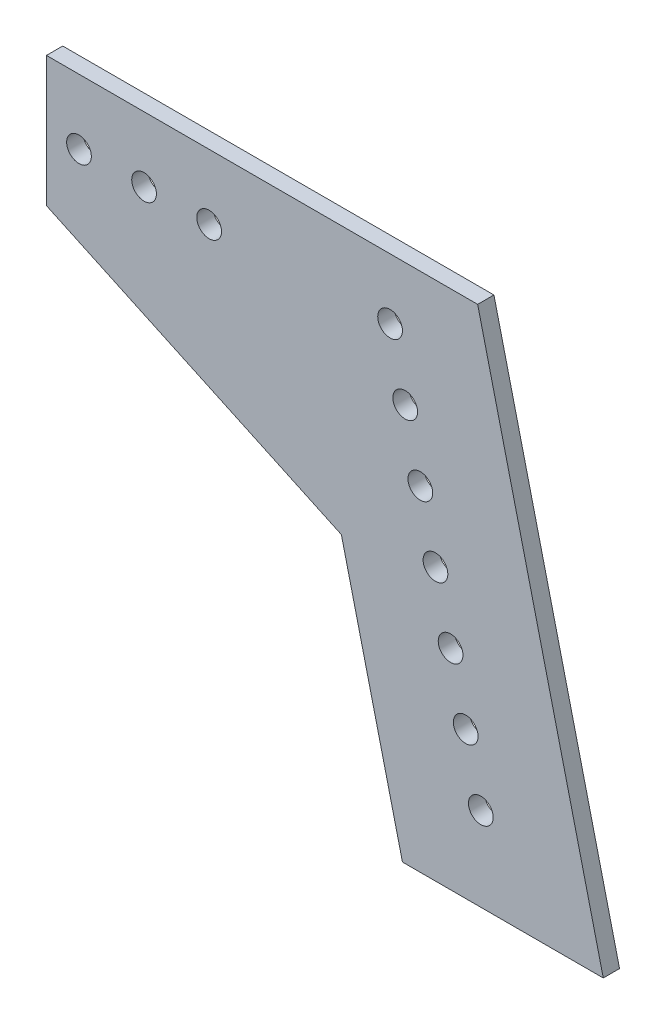
SolidWorks part; units mm, degrees
ref_plane "Front Plane" through (0, 0, 0) normal (0, 0, 1) x (1, 0, 0)
ref_plane "Top Plane" through (0, 0, 0) normal (0, 1, 0) x (1, 0, 0)
ref_plane "Right Plane" through (0, 0, 0) normal (1, 0, 0) x (0, 0, -1)
sketch "Sketch1" plane through (0, 0, 0) normal (0, 0, 1) x (1, 0, 0)
  line L1 (-190.5, -88.9) -> (190.5, -88.9)
  line L2 (-190.5, -88.9) -> (-190.5, 88.9)
  line L3 (-190.5, 88.9) -> (190.5, 88.9)
  line L4 (190.5, -88.9) -> (190.5, 88.9)
  dimension "D1" = 381
  dimension "D2" = 177.8
extrude "Boss-Extrude1" add sketch "Sketch1" along normal blind 3.175
sketch "Sketch3" plane through (0, 0, 0) normal (0, 0, -1) x (-1, 0, 0)
  line L7 (-133.1401, -83.5308) -> (-95.5604, 72.2062) construction
  line L8 (-223.5893, -458.3689) -> (-104.4279, 35.4576) construction
  line L9 (187.2332, -70.9445) -> (149.6535, 84.7925) construction
  line L10 (161.6214, 35.1951) -> (280.6439, -458.0557) construction
  line L11 (-190.5, 88.9) -> (-99.3708, 88.9)
  line L12 (-190.5, 88.9) -> (190.5, 88.9) construction
  line L13 (-99.3708, 88.9) -> (-190.5, -288.7557)
  line L14 (-190.5, -288.7557) -> (-190.5, 88.9)
  line L15 (258.6308, 88.9) -> (156.501, 88.9)
  line L16 (156.501, 88.9) -> (258.6308, -334.3442)
  line L17 (258.6308, -334.3442) -> (258.6308, 88.9)
  dimension "D1" = 7.62
  dimension "D2" = 7.62
extrude "Cut-Extrude1" cut sketch "Sketch3" against normal through all
sketch "Sketch4" plane through (0, 0, 0) normal (0, 0, -1) x (-1, 0, 0)
  line L0 (201.949, -63.5) -> (-149.0579, -63.5)
  line L3 (-149.0579, -63.5) -> (-154.4804, -88.9)
  line L4 (-154.4804, -88.9) -> (207.1627, -88.9)
  line L5 (207.1627, -88.9) -> (201.949, -63.5)
  line L6 (190.5, -88.9) -> (-142.2744, -88.9) construction
  dimension "D1" = 25.4
extrude "Cut-Extrude2" cut sketch "Sketch4" against normal through all
sketch "Sketch8" plane through (0, 0, 0) normal (0, 0, -1) x (-1, 0, 0)
  line L0 (-96.9518, -63.5) -> (-85.0324, -14.1181)
  line L1 (190.5, -63.5) -> (-136.1453, -63.5) construction
  line L2 (-85.0324, -14.1181) -> (194.3676, -14.1181)
  line L3 (194.3676, -14.1181) -> (206.287, -63.5)
  line L4 (206.287, -63.5) -> (-96.9518, -63.5)
  dimension "D2" = 103.57
  dimension "D3" = 279.4
  dimension "D4" = 50.8
  dimension "D5" = 76.43
extrude "Cut-Extrude3" cut sketch "Sketch8" against normal through all
sketch "Sketch9" plane through (0, 0, 0) normal (0, 0, -1) x (-1, 0, 0)
  line L0 (-117.7822, -70.0483) -> (-79.4277, 88.9) construction
  line L1 (-99.3708, 88.9) -> (156.501, 88.9) construction
  line L4 (-136.1453, -63.5) -> (-99.3708, 88.9) construction
  line L5 (-136.1453, -63.5) -> (-99.3708, 88.9) construction
  circle A0 centre (-112.2489, -47.117) radius 2.413
  circle A1 centre (-109.2968, -34.8832) radius 2.413
  circle A2 centre (-106.3448, -22.6495) radius 2.413
  circle A3 centre (-103.3928, -10.4158) radius 2.413
  circle A4 centre (-100.4407, 1.818) radius 2.413
  circle A5 centre (-97.4887, 14.0517) radius 2.413
  circle A6 centre (-94.5367, 26.2855) radius 2.413
  circle A7 centre (-91.5847, 38.5192) radius 2.413 construction
  circle A8 centre (-88.6326, 50.753) radius 2.413 construction
  circle A9 centre (-85.6806, 62.9867) radius 2.413
  circle A10 centre (-82.7286, 75.2205) radius 2.413
  ellipse E0 centre (-117.4825, -72.4407) end of major axis (-116.9164, -70.095) minor radius 2.3977 construction
  dimension "D1" = 4.826
  dimension "D2" = 19.3868
  dimension "D4" = 13.6795
  dimension "D3" = 11
extrude "Cut-Extrude5" cut sketch "Sketch9" against normal through all
sketch "Sketch10" plane through (0, 0, 0) normal (0, 0, -1) x (-1, 0, 0)
  line L0 (-99.3708, 88.9) -> (-111.629, 38.1)
  line L1 (-136.1453, -63.5) -> (-99.3708, 88.9) construction
  line L2 (-111.629, 38.1) -> (168.7592, 38.1)
  line L4 (156.501, 88.9) -> (181.3595, -14.1181) construction
  line L5 (168.7592, 38.1) -> (156.501, 88.9)
  line L6 (156.501, 88.9) -> (-99.3708, 88.9)
  dimension "D1" = 50.8
extrude "Cut-Extrude6" cut sketch "Sketch10" against normal through all
sketch "Sketch11" plane through (0, 0, 0) normal (0, 0, -1) x (-1, 0, 0)
  line L0 (-85.0324, -14.1181) -> (-27.4734, 12.7)
  line L1 (-27.4734, 12.7) -> (-27.4734, 38.1)
  line L2 (-111.629, 38.1) -> (168.7592, 38.1) construction
  line L5 (-27.4734, 38.1) -> (60.9592, 38.1)
  line L6 (132.284, -14.1181) -> (-85.0324, -14.1181)
  line L7 (60.9592, 38.1) -> (169.9103, 38.1)
  line L8 (169.9103, 38.1) -> (200.7912, -67.4952)
  line L9 (200.7912, -67.4952) -> (145.1677, -67.4952)
  line L10 (145.1677, -67.4952) -> (132.284, -14.1181)
  point P2 (169.9103, 38.1)
  point P7 (200.7912, -67.4952)
  dimension "D1" = 25.4
  dimension "D2" = 63.5
extrude "Cut-Extrude7" cut sketch "Sketch11" against normal through all
sketch "Sketch12" plane through (0, 0, 0) normal (0, 0, -1) x (-1, 0, 0)
  line L0 (-27.4734, 38.1) -> (-27.4734, 12.7) construction
  line L1 (-65.5734, 12.7) -> (124.9266, 12.7) construction
  circle A0 centre (-33.8234, 25.4) radius 2.413
  circle A1 centre (-46.5234, 25.4) radius 2.413
  circle A2 centre (-59.2234, 25.4) radius 2.413
  dimension "D1" = 4.826
  dimension "D2" = 6.35
  dimension "D3" = 12.7
  dimension "D4" = 3
extrude "Cut-Extrude8" cut sketch "Sketch12" against normal through all
sketch "Sketch7" plane through (0, 0, 0) normal (0, 0, -1) x (-1, 0, 0)
  line L0 (-142.1813, -63.5) -> (-127.8939, -16.9599)
  line L1 (179.0525, -63.5) -> (-177.122, -63.5) construction
  line L2 (-127.8939, -16.9599) -> (126.8526, -16.9599)
  line L3 (126.8526, -16.9599) -> (140.6477, -63.5)
  line L4 (140.6477, -63.5) -> (-142.1813, -63.5)
sketch "Sketch6" plane through (0, 0, 0) normal (0, 0, -1) x (-1, 0, 0)
  line L0 (-140.8106, -63.5) -> (-127.3051, -19.1804)
  line L1 (179.0525, -63.5) -> (-177.122, -63.5) construction
  line L2 (-127.3051, -19.1804) -> (124.3177, -19.1804)
  line L3 (124.3177, -19.1804) -> (136.9873, -63.5)
